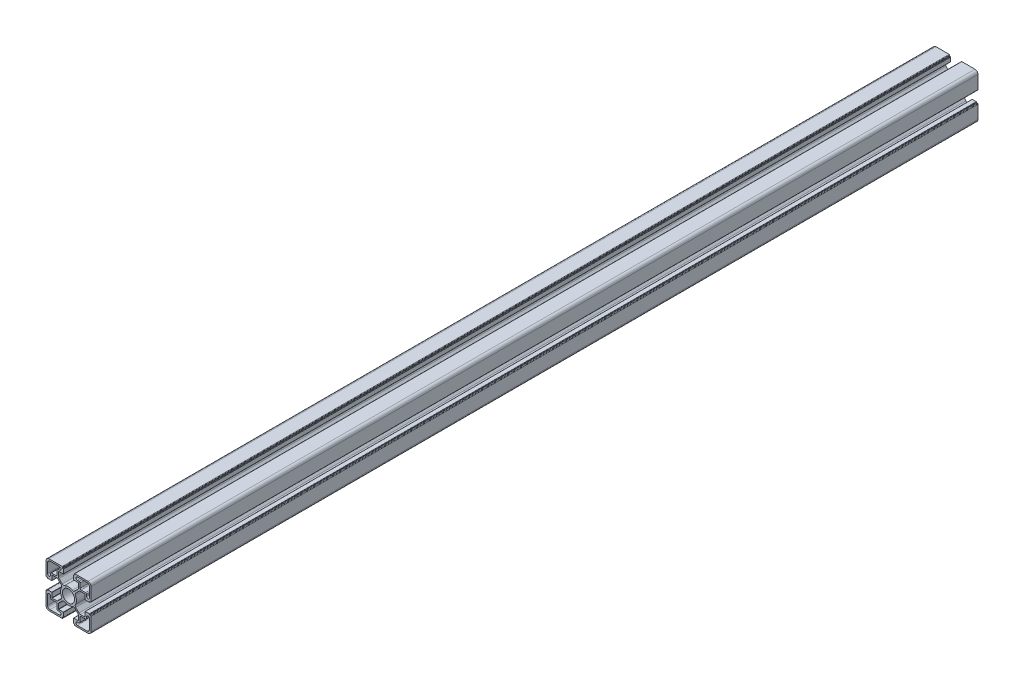
SolidWorks part; units mm, degrees
ref_plane "Front Plane" through (0, 0, 0) normal (0, 0, 1) x (1, 0, 0)
ref_plane "Top Plane" through (0, 0, 0) normal (0, 1, 0) x (1, 0, 0)
ref_plane "Right Plane" through (0, 0, 0) normal (1, 0, 0) x (0, 0, -1)
sketch "Sketch1" plane through (0, 0, 0) normal (0, 0, 1) x (1, 0, 0)
  line L3 (-22.5, 19.5) -> (-22.5, 6.3)
  line L4 (-20.7, 5) -> (-16.7, 5)
  line L5 (-16.5, 5.2) -> (-16.5, 9.8)
  line L6 (-16.3, 10) -> (-11.8642, 10)
  line L7 (-10.4924, 9.4318) -> (-7.2967, 6.236)
  line L8 (-21, 18.5) -> (-21, 9)
  line L9 (-16.5, 5) -> (-16.5, 10) construction
  line L10 (-18, 9) -> (-18, 10.5)
  line L11 (-17, 11.5) -> (-12.5, 11.5)
  line L12 (-22, 5.8) -> (-21.3, 5.8)
  line L13 (-21, 5.5) -> (-21, 5.3)
  line L14 (-21, 22.5) -> (-21, 6.5) construction
  line L15 (-18, 11.5) -> (-10.4393, 11.5) construction
  line L16 (-10.4393, 11.5) -> (-5.1016, 6.1623) construction
  line L17 (-18, 6.5) -> (-18, 11.5) construction
  line L18 (-22.5, 22.5) -> (-22.5, 5) construction
  line L19 (-22.5, 5) -> (-16.5, 5) construction
  line L20 (-21, 6.5) -> (-18, 6.5) construction
  line L21 (-16.5, 10) -> (-11.0607, 10) construction
  line L22 (-11.0607, 10) -> (-6.1623, 5.1016) construction
  line L23 (-5.5, 21) -> (-5.3, 21)
  line L24 (-5.8, 22) -> (-5.8, 21.3)
  line L25 (-11.5, 17) -> (-11.5, 12.5)
  line L26 (-9, 18) -> (-10.5, 18)
  line L27 (-18.5, 21) -> (-9, 21)
  line L28 (-9.4318, 10.4924) -> (-6.236, 7.2967)
  line L29 (-10, 16.3) -> (-10, 11.8642)
  line L30 (-5.2, 16.5) -> (-9.8, 16.5)
  line L31 (-5, 20.7) -> (-5, 16.7)
  line L32 (-19.5, 22.5) -> (-6.3, 22.5)
  line L33 (19.5, 22.5) -> (6.3, 22.5)
  line L34 (5, 20.7) -> (5, 16.7)
  line L35 (5.2, 16.5) -> (9.8, 16.5)
  line L36 (10, 16.3) -> (10, 11.8642)
  line L37 (9.4318, 10.4924) -> (6.236, 7.2967)
  line L38 (18.5, 21) -> (9, 21)
  line L39 (9, 18) -> (10.5, 18)
  line L40 (11.5, 17) -> (11.5, 12.5)
  line L41 (5.8, 22) -> (5.8, 21.3)
  line L42 (5.5, 21) -> (5.3, 21)
  line L43 (21, 5.5) -> (21, 5.3)
  line L44 (22, 5.8) -> (21.3, 5.8)
  line L45 (17, 11.5) -> (12.5, 11.5)
  line L46 (18, 9) -> (18, 10.5)
  line L47 (21, 18.5) -> (21, 9)
  line L48 (10.4924, 9.4318) -> (7.2967, 6.236)
  line L49 (16.3, 10) -> (11.8642, 10)
  line L50 (16.5, 5.2) -> (16.5, 9.8)
  line L51 (20.7, 5) -> (16.7, 5)
  line L52 (22.5, 19.5) -> (22.5, 6.3)
  line L53 (22.5, -19.5) -> (22.5, -6.3)
  line L54 (20.7, -5) -> (16.7, -5)
  line L55 (16.5, -5.2) -> (16.5, -9.8)
  line L56 (16.3, -10) -> (11.8642, -10)
  line L57 (10.4924, -9.4318) -> (7.2967, -6.236)
  line L58 (21, -18.5) -> (21, -9)
  line L59 (18, -9) -> (18, -10.5)
  line L60 (17, -11.5) -> (12.5, -11.5)
  line L61 (22, -5.8) -> (21.3, -5.8)
  line L62 (21, -5.5) -> (21, -5.3)
  line L63 (5.5, -21) -> (5.3, -21)
  line L64 (5.8, -22) -> (5.8, -21.3)
  line L65 (11.5, -17) -> (11.5, -12.5)
  line L66 (9, -18) -> (10.5, -18)
  line L67 (18.5, -21) -> (9, -21)
  line L68 (9.4318, -10.4924) -> (6.236, -7.2967)
  line L69 (10, -16.3) -> (10, -11.8642)
  line L70 (5.2, -16.5) -> (9.8, -16.5)
  line L71 (5, -20.7) -> (5, -16.7)
  line L72 (19.5, -22.5) -> (6.3, -22.5)
  line L73 (-19.5, -22.5) -> (-6.3, -22.5)
  line L74 (-5, -20.7) -> (-5, -16.7)
  line L75 (-5.2, -16.5) -> (-9.8, -16.5)
  line L76 (-10, -16.3) -> (-10, -11.8642)
  line L77 (-9.4318, -10.4924) -> (-6.236, -7.2967)
  line L78 (-18.5, -21) -> (-9, -21)
  line L79 (-9, -18) -> (-10.5, -18)
  line L80 (-11.5, -17) -> (-11.5, -12.5)
  line L81 (-5.8, -22) -> (-5.8, -21.3)
  line L82 (-5.5, -21) -> (-5.3, -21)
  line L83 (-21, -5.5) -> (-21, -5.3)
  line L84 (-22, -5.8) -> (-21.3, -5.8)
  line L85 (-17, -11.5) -> (-12.5, -11.5)
  line L86 (-18, -9) -> (-18, -10.5)
  line L87 (-21, -18.5) -> (-21, -9)
  line L88 (-10.4924, -9.4318) -> (-7.2967, -6.236)
  line L89 (-16.3, -10) -> (-11.8642, -10)
  line L90 (-16.5, -5.2) -> (-16.5, -9.8)
  line L91 (-20.7, -5) -> (-16.7, -5)
  line L92 (-22.5, -19.5) -> (-22.5, -6.3)
  arc A0 (0, 6.1) -> (-6.1, 0) centre (0, 0) ccw
  arc A1 (-6.9766, 3.9149) -> (-8, 0) centre (0, 0) ccw
  arc A2 (-21, 9) -> (-18, 9) centre (-19.5, 9) ccw
  arc A3 (-22, 5.8) -> (-22.5, 6.3) centre (-22, 6.3) cw
  arc A4 (-21, 5.3) -> (-20.7, 5) centre (-20.7, 5.3) ccw
  arc A5 (-21.3, 5.8) -> (-21, 5.5) centre (-21.3, 5.5) cw
  arc A6 (-16.7, 5) -> (-16.5, 5.2) centre (-16.7, 5.2) ccw
  arc A7 (-16.5, 9.8) -> (-16.3, 10) centre (-16.3, 9.8) cw
  arc A8 (-7.2967, 6.236) -> (-6.9766, 3.9149) centre (-8.6685, 4.8643) cw
  arc A9 (-11.8642, 10) -> (-10.4924, 9.4318) centre (-11.8642, 8.06) cw
  arc A10 (-18, 10.5) -> (-17, 11.5) centre (-17, 10.5) cw
  arc A11 (-10.5, 18) -> (-11.5, 17) centre (-10.5, 17) ccw
  arc A12 (-10, 11.8642) -> (-9.4318, 10.4924) centre (-8.06, 11.8642) ccw
  arc A13 (-6.236, 7.2967) -> (-3.9149, 6.9766) centre (-4.8643, 8.6685) ccw
  arc A14 (-9.8, 16.5) -> (-10, 16.3) centre (-9.8, 16.3) ccw
  arc A15 (-5, 16.7) -> (-5.2, 16.5) centre (-5.2, 16.7) cw
  arc A16 (-5.8, 21.3) -> (-5.5, 21) centre (-5.5, 21.3) ccw
  arc A17 (-5.3, 21) -> (-5, 20.7) centre (-5.3, 20.7) cw
  arc A18 (-5.8, 22) -> (-6.3, 22.5) centre (-6.3, 22) ccw
  arc A19 (-9, 21) -> (-9, 18) centre (-9, 19.5) cw
  arc A20 (-3.9149, 6.9766) -> (0, 8) centre (0, 0) cw
  arc A21 (-21, 18.5) -> (-18.5, 21) centre (-18.5, 18.5) cw
  arc A22 (-22.5, 19.5) -> (-19.5, 22.5) centre (-19.5, 19.5) cw
  arc A23 (-12.5, 11.5) -> (-11.5, 12.5) centre (-12.5, 12.5) ccw
  arc A24 (6.1, 0) -> (0, 6.1) centre (0, 0) ccw
  arc A25 (3.9149, 6.9766) -> (0, 8) centre (0, 0) ccw
  arc A26 (9, 21) -> (9, 18) centre (9, 19.5) ccw
  arc A27 (5.8, 22) -> (6.3, 22.5) centre (6.3, 22) cw
  arc A28 (5.3, 21) -> (5, 20.7) centre (5.3, 20.7) ccw
  arc A29 (5.8, 21.3) -> (5.5, 21) centre (5.5, 21.3) cw
  arc A30 (5, 16.7) -> (5.2, 16.5) centre (5.2, 16.7) ccw
  arc A31 (9.8, 16.5) -> (10, 16.3) centre (9.8, 16.3) cw
  arc A32 (6.236, 7.2967) -> (3.9149, 6.9766) centre (4.8643, 8.6685) cw
  arc A33 (10, 11.8642) -> (9.4318, 10.4924) centre (8.06, 11.8642) cw
  arc A34 (10.5, 18) -> (11.5, 17) centre (10.5, 17) cw
  arc A35 (18, 10.5) -> (17, 11.5) centre (17, 10.5) ccw
  arc A36 (11.8642, 10) -> (10.4924, 9.4318) centre (11.8642, 8.06) ccw
  arc A37 (7.2967, 6.236) -> (6.9766, 3.9149) centre (8.6685, 4.8643) ccw
  arc A38 (16.5, 9.8) -> (16.3, 10) centre (16.3, 9.8) ccw
  arc A39 (16.7, 5) -> (16.5, 5.2) centre (16.7, 5.2) cw
  arc A40 (21.3, 5.8) -> (21, 5.5) centre (21.3, 5.5) ccw
  arc A41 (21, 5.3) -> (20.7, 5) centre (20.7, 5.3) cw
  arc A42 (22, 5.8) -> (22.5, 6.3) centre (22, 6.3) ccw
  arc A43 (21, 9) -> (18, 9) centre (19.5, 9) cw
  arc A44 (6.9766, 3.9149) -> (8, 0) centre (0, 0) cw
  arc A45 (18.5, 21) -> (21, 18.5) centre (18.5, 18.5) cw
  arc A46 (19.5, 22.5) -> (22.5, 19.5) centre (19.5, 19.5) cw
  arc A47 (11.5, 12.5) -> (12.5, 11.5) centre (12.5, 12.5) ccw
  arc A48 (0, -6.1) -> (6.1, 0) centre (0, 0) ccw
  arc A49 (6.9766, -3.9149) -> (8, 0) centre (0, 0) ccw
  arc A50 (21, -9) -> (18, -9) centre (19.5, -9) ccw
  arc A51 (22, -5.8) -> (22.5, -6.3) centre (22, -6.3) cw
  arc A52 (21, -5.3) -> (20.7, -5) centre (20.7, -5.3) ccw
  arc A53 (21.3, -5.8) -> (21, -5.5) centre (21.3, -5.5) cw
  arc A54 (16.7, -5) -> (16.5, -5.2) centre (16.7, -5.2) ccw
  arc A55 (16.5, -9.8) -> (16.3, -10) centre (16.3, -9.8) cw
  arc A56 (7.2967, -6.236) -> (6.9766, -3.9149) centre (8.6685, -4.8643) cw
  arc A57 (11.8642, -10) -> (10.4924, -9.4318) centre (11.8642, -8.06) cw
  arc A58 (18, -10.5) -> (17, -11.5) centre (17, -10.5) cw
  arc A59 (10.5, -18) -> (11.5, -17) centre (10.5, -17) ccw
  arc A60 (10, -11.8642) -> (9.4318, -10.4924) centre (8.06, -11.8642) ccw
  arc A61 (6.236, -7.2967) -> (3.9149, -6.9766) centre (4.8643, -8.6685) ccw
  arc A62 (9.8, -16.5) -> (10, -16.3) centre (9.8, -16.3) ccw
  arc A63 (5, -16.7) -> (5.2, -16.5) centre (5.2, -16.7) cw
  arc A64 (5.8, -21.3) -> (5.5, -21) centre (5.5, -21.3) ccw
  arc A65 (5.3, -21) -> (5, -20.7) centre (5.3, -20.7) cw
  arc A66 (5.8, -22) -> (6.3, -22.5) centre (6.3, -22) ccw
  arc A67 (9, -21) -> (9, -18) centre (9, -19.5) cw
  arc A68 (3.9149, -6.9766) -> (0, -8) centre (0, 0) cw
  arc A69 (21, -18.5) -> (18.5, -21) centre (18.5, -18.5) cw
  arc A70 (22.5, -19.5) -> (19.5, -22.5) centre (19.5, -19.5) cw
  arc A71 (12.5, -11.5) -> (11.5, -12.5) centre (12.5, -12.5) ccw
  arc A72 (-6.1, 0) -> (0, -6.1) centre (0, 0) ccw
  arc A73 (-3.9149, -6.9766) -> (0, -8) centre (0, 0) ccw
  arc A74 (-9, -21) -> (-9, -18) centre (-9, -19.5) ccw
  arc A75 (-5.8, -22) -> (-6.3, -22.5) centre (-6.3, -22) cw
  arc A76 (-5.3, -21) -> (-5, -20.7) centre (-5.3, -20.7) ccw
  arc A77 (-5.8, -21.3) -> (-5.5, -21) centre (-5.5, -21.3) cw
  arc A78 (-5, -16.7) -> (-5.2, -16.5) centre (-5.2, -16.7) ccw
  arc A79 (-9.8, -16.5) -> (-10, -16.3) centre (-9.8, -16.3) cw
  arc A80 (-6.236, -7.2967) -> (-3.9149, -6.9766) centre (-4.8643, -8.6685) cw
  arc A81 (-10, -11.8642) -> (-9.4318, -10.4924) centre (-8.06, -11.8642) cw
  arc A82 (-10.5, -18) -> (-11.5, -17) centre (-10.5, -17) cw
  arc A83 (-18, -10.5) -> (-17, -11.5) centre (-17, -10.5) ccw
  arc A84 (-11.8642, -10) -> (-10.4924, -9.4318) centre (-11.8642, -8.06) ccw
  arc A85 (-7.2967, -6.236) -> (-6.9766, -3.9149) centre (-8.6685, -4.8643) ccw
  arc A86 (-16.5, -9.8) -> (-16.3, -10) centre (-16.3, -9.8) ccw
  arc A87 (-16.7, -5) -> (-16.5, -5.2) centre (-16.7, -5.2) cw
  arc A88 (-21.3, -5.8) -> (-21, -5.5) centre (-21.3, -5.5) ccw
  arc A89 (-21, -5.3) -> (-20.7, -5) centre (-20.7, -5.3) cw
  arc A90 (-22, -5.8) -> (-22.5, -6.3) centre (-22, -6.3) ccw
  arc A91 (-21, -9) -> (-18, -9) centre (-19.5, -9) cw
  arc A92 (-6.9766, -3.9149) -> (-8, 0) centre (0, 0) cw
  arc A93 (-18.5, -21) -> (-21, -18.5) centre (-18.5, -18.5) cw
  arc A94 (-19.5, -22.5) -> (-22.5, -19.5) centre (-19.5, -19.5) cw
  arc A95 (-11.5, -12.5) -> (-12.5, -11.5) centre (-12.5, -12.5) ccw
  point P24 (-5.8, 21)
  point P32 (-22.5, 5.8)
  point P35 (-21, 5)
  point P38 (-21, 5.8)
  point P83 (-5, 21)
  point P84 (-5.8, 22.5)
  point P87 (-21, 21)
  point P93 (-11.5, 11.5)
  point P102 (21, 5.8)
  point P158 (21, 5)
  point P159 (22.5, 5.8)
  point P172 (5.8, -21)
  point P228 (5, -21)
  point P229 (5.8, -22.5)
  point P242 (-21, -5.8)
  point P298 (-21, -5)
  point P299 (-22.5, -5.8)
  dimension "D11" = 0.5
  dimension "D12" = 0.3
  dimension "D13" = 0.2
  dimension "D14" = 0.2
  dimension "D6" = 1.94
  dimension "D15" = 1
  dimension "D16" = 2.5
  dimension "D4" = 3
  dimension "D17" = 1
  dimension "D5" = 0.8
  dimension "D7" = 1.5
  dimension "D9" = 1.5
  dimension "D10" = 4
  dimension "D18" = 4
extrude "Boss-Extrude1" add sketch "Sketch1" along normal blind 500.8
scale "Scale2" scale about centroid uniform scaling no x scale factor 0.564444 y scale factor 0.564444 z scale factor 1
